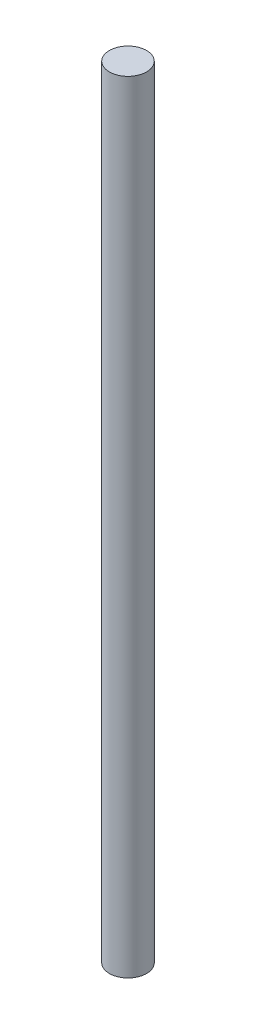
SolidWorks part; units mm, degrees
material "Plain Carbon Steel"
ref_plane "Front Plane" through (0, 0, 0) normal (0, 0, 1) x (1, 0, 0)
ref_plane "Top Plane" through (0, 0, 0) normal (0, 1, 0) x (1, 0, 0)
ref_plane "Right Plane" through (0, 0, 0) normal (1, 0, 0) x (0, 0, -1)
sketch "Sketch1" plane through (0, 0, 0) normal (0, 1, 0) x (1, 0, 0)
  circle A0 centre (0, 0) radius 4.7625
  dimension "D1" = 9.525
extrude "Boss-Extrude1" add sketch "Sketch1" along normal blind 200
ref_axis "Axis1" through (0, 210, 0) along (0, -1, 0)
